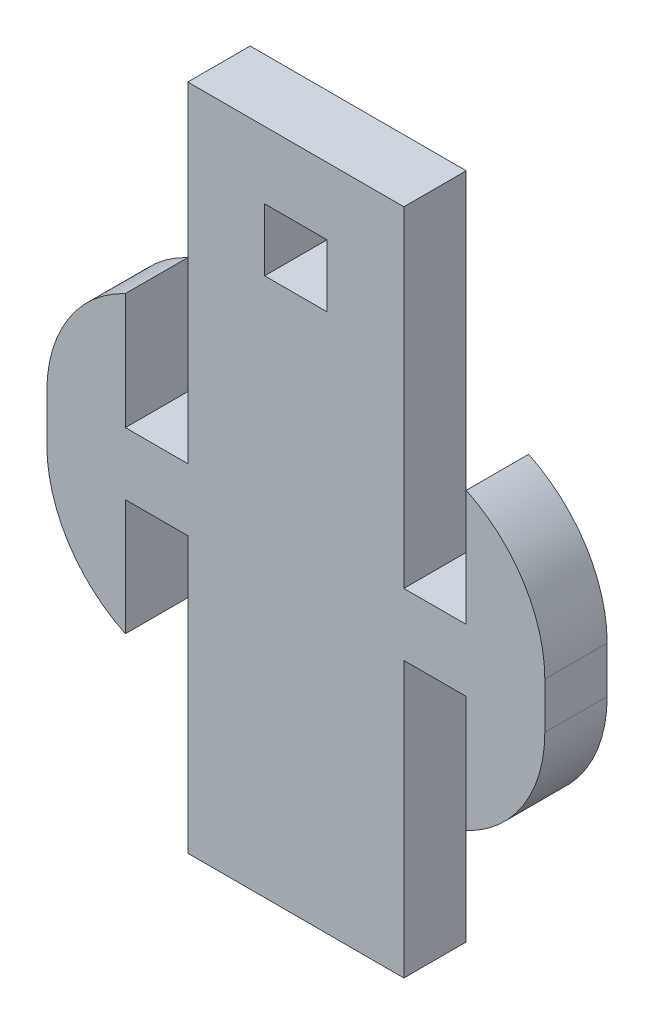
SolidWorks part; units mm, degrees
ref_plane "Front Plane" through (0, 0, 0) normal (0, 0, 1) x (1, 0, 0)
ref_plane "Top Plane" through (0, 0, 0) normal (0, 1, 0) x (1, 0, 0)
ref_plane "Right Plane" through (0, 0, 0) normal (1, 0, 0) x (0, 0, -1)
sketch "Sketch1" plane through (0, 0, 0) normal (0, 0, 1) x (1, 0, 0)
  line L0 (3, 45.5624) -> (-3, 45.5624)
  line L1 (-63.3907, 0) -> (63.762, 0) construction
  line L2 (3, 45.5624) -> (5.5, 45.5624)
  line L3 (5.5, 79.5624) -> (5.5, 62.7374)
  line L4 (-5.5, 59.5624) -> (5.5, 59.5624) construction
  line L5 (5.5, 59.5624) -> (8.675, 59.5624)
  line L6 (8.675, 59.5624) -> (8.675, 62.7374)
  line L7 (8.675, 62.7374) -> (5.5, 62.7374)
  line L8 (5.5, 59.5624) -> (5.5, 45.5624)
  line L9 (-5.5, 45.5624) -> (-3, 45.5624) construction
  line L10 (-5.5, 59.5624) -> (-5.5, 45.5624)
  line L11 (-8.675, 62.7374) -> (-5.5, 62.7374)
  line L12 (-8.675, 59.5624) -> (-8.675, 62.7374)
  line L13 (-5.5, 59.5624) -> (-8.675, 59.5624)
  line L14 (-5.5, 79.5624) -> (5.5, 79.5624)
  line L15 (0, 45.5624) -> (0, 85.4214) construction
  line L16 (-5.5, 79.5624) -> (-5.5, 62.7374)
  line L17 (-3, 45.5624) -> (-5.5, 45.5624)
  line L32 (5.5, 45.5624) -> (3, 45.5624) construction
  point P15 (0, 59.5624)
  point P17 (0, 79.5624)
  dimension "D1" = 34
  dimension "D2" = 5.5
  dimension "D3" = 3.175
  dimension "D4" = 3.175
extrude "Boss-Extrude1" add sketch "Sketch1" along normal blind 3.175
sketch "Sketch2" plane through (0, 0, 0) normal (0, 0, -1) x (-1, 0, 0)
  line L0 (-5.5, 69.5624) -> (5.5, 69.5624) construction
  line L1 (-5.5, 62.7374) -> (-5.5, 79.5624) construction
  line L2 (5.5, 79.5624) -> (5.5, 62.7374) construction
  line L3 (-5.5, 79.5624) -> (5.5, 79.5624) construction
  line L4 (-5.5, 69.5624) -> (5.5, 79.5624) construction
  line L6 (1.5875, 72.9749) -> (-1.5875, 72.9749)
  line L7 (1.5875, 72.9749) -> (1.5875, 76.1499)
  line L8 (1.5875, 76.1499) -> (-1.5875, 76.1499)
  line L9 (-1.5875, 72.9749) -> (-1.5875, 76.1499)
  line L10 (1.5875, 72.9749) -> (-1.5875, 76.1499) construction
  line L11 (1.5875, 76.1499) -> (-1.5875, 72.9749) construction
  point P8 (0, 74.5624)
  dimension "D1" = 10
  dimension "D2" = 3.175
  dimension "D3" = 3.175
extrude "Cut-Extrude1" cut sketch "Sketch2" against normal through all
sketch "Sketch3" plane through (-8.675, 0, 0) normal (-1, 0, 0) x (0, 0, 1)
  line L0 (3.175, 59.5624) -> (0, 62.7374) construction
  line L1 (0, 79.5624) -> (0, 62.7374) construction
  line L2 (3.175, 53.6499) -> (0, 53.6499)
  line L3 (3.175, 53.6499) -> (3.175, 68.6499)
  line L4 (3.175, 68.6499) -> (0, 68.6499)
  line L5 (0, 53.6499) -> (0, 68.6499)
  line L6 (3.175, 53.6499) -> (0, 68.6499) construction
  line L7 (3.175, 68.6499) -> (0, 53.6499) construction
  point P4 (1.5875, 61.1499)
  dimension "D1" = 15
extrude "Boss-Extrude2" add sketch "Sketch3" along normal blind 4
mirror "Mirror2" about plane through (0, 0, 0) normal (1, 0, 0) of "Boss-Extrude2"
fillet "Fillet1" radius 7 4 edges at (-12.675, 68.6499, 1.5875) (-12.675, 53.6499, 1.5875) (12.675, 68.6499, 1.5875) (12.675, 53.6499, 1.5875)
